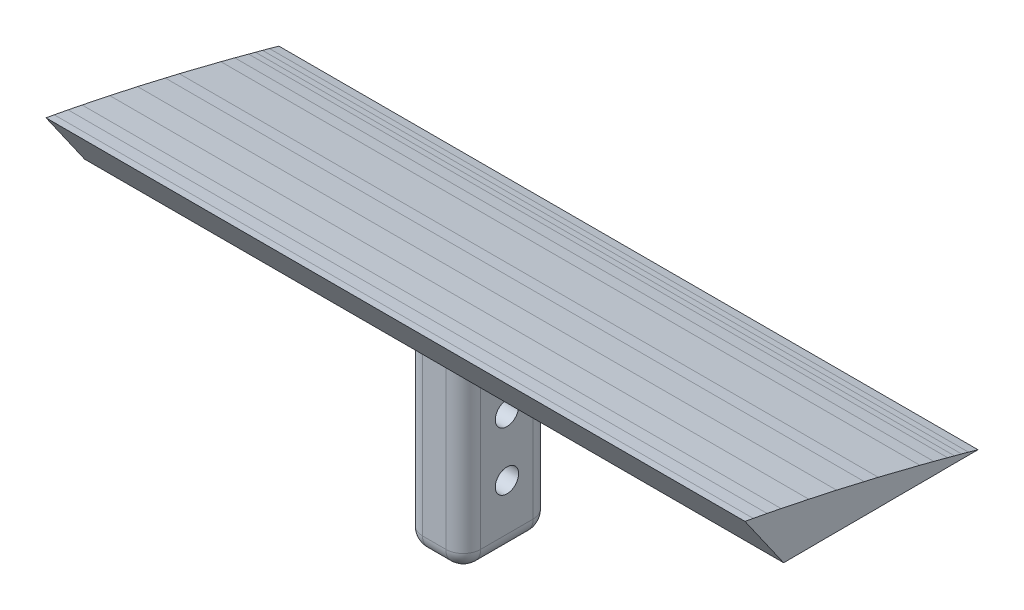
SolidWorks part; units mm, degrees
material "LW PLA"
ref_plane "Front Plane" through (0, 0, 0) normal (0, 0, 1) x (1, 0, 0)
ref_plane "Top Plane" through (0, 0, 0) normal (0, 1, 0) x (1, 0, 0)
ref_plane "Right Plane" through (0, 0, 0) normal (1, 0, 0) x (0, 0, -1)
sketch "Sketch4" plane through (0, 0, 0) normal (1, 0, 0) x (0, 0, -1)
  line L123 (0, 0) -> (68.4812, 0) construction
  line B0 (45.1998, 6.9232) -> (45.1998, 2.1781) construction
  line B1 (65.1998, 2.25) -> (64.3732, 2.4866)
  line B2 (64.3732, 2.4866) -> (63.783, 2.6455)
  line B3 (63.783, 2.6455) -> (63.1827, 2.8045)
  line B4 (63.1827, 2.8045) -> (62.5924, 2.9634)
  line B5 (62.5924, 2.9634) -> (61.4018, 3.2813)
  line B6 (61.4018, 3.2813) -> (60.2113, 3.5892)
  line B7 (60.2113, 3.5892) -> (59.0208, 3.8871)
  line B8 (59.0208, 3.8871) -> (57.8302, 4.185)
  line B9 (57.8302, 4.185) -> (56.6397, 4.4829)
  line B10 (56.6397, 4.4829) -> (55.4392, 4.7608)
  line B11 (55.4392, 4.7608) -> (54.2487, 5.0387)
  line B12 (54.2487, 5.0387) -> (53.0582, 5.3166)
  line B13 (53.0582, 5.3166) -> (51.8678, 5.5745)
  line B14 (51.8678, 5.5745) -> (50.6773, 5.8324)
  line B15 (50.6773, 5.8324) -> (49.4869, 6.0803)
  line B16 (49.4869, 6.0803) -> (48.2964, 6.3282)
  line B17 (48.2964, 6.3282) -> (47.096, 6.5661)
  line B18 (47.096, 6.5661) -> (45.9056, 6.794)
  line B19 (45.9056, 6.794) -> (45.1998, 6.9232)
  line B20 (45.1998, 2.1781) -> (45.7538, 2.1837) construction
  line B21 (45.7538, 2.1837) -> (46.9537, 2.1858) construction
  line B22 (46.9537, 2.1858) -> (48.1537, 2.1879) construction
  line B23 (48.1537, 2.1879) -> (48.515, 2.1886) construction
  line B24 (49.3537, 2.19) -> (50.5537, 2.1922)
  line B25 (50.5537, 2.1922) -> (51.7537, 2.2043)
  line B26 (51.7537, 2.2043) -> (52.9537, 2.2064)
  line B27 (52.9537, 2.2064) -> (54.1537, 2.2085)
  line B28 (54.1537, 2.2085) -> (55.3637, 2.2107)
  line B29 (55.3637, 2.2107) -> (56.5637, 2.2128)
  line B30 (56.5637, 2.2128) -> (57.7637, 2.2249)
  line B31 (57.7637, 2.2249) -> (58.9637, 2.227)
  line B32 (58.9637, 2.227) -> (60.1637, 2.2291)
  line B33 (60.1637, 2.2291) -> (61.3637, 2.2313)
  line B34 (61.3637, 2.2313) -> (62.5637, 2.2434)
  line B35 (62.5637, 2.2434) -> (63.1637, 2.2444)
  line B36 (63.1637, 2.2444) -> (63.7637, 2.2455)
  line B37 (63.7637, 2.2455) -> (64.3637, 2.2466)
  line B38 (64.3637, 2.2466) -> (64.9637, 2.2476)
  line B39 (5, 4.2717) -> (65.0821, 2.2837) construction
  line B40 (64.9637, 2.2476) -> (65.1998, 2.25)
  line B41 (45.1998, 6.9232) -> (48.515, 2.1886)
  line B42 (48.515, 2.1886) -> (49.3537, 2.19)
  dimension "D1" = 1.895
sketch_block_instance "Block2-1"
sketch_block "Block2" parameters "D1"=20, "D2"=3.6418
extrude "Boss-Extrude1" add sketch "Sketch4" along normal blind 60
ref_plane "Plane1" through (0, 2.1886, 0) normal (0, 1, 0) x (1, 0, 0)
sketch "Sketch5" plane through (0, 2.1886, 0) normal (0, 1, 0) x (1, 0, 0)
  line L0 (60, 48.515) -> (0, 48.515) construction
  line L1 (27.5, 48.515) -> (32.5, 48.515)
  line L2 (27.5, 48.515) -> (27.5, 56.015)
  line L3 (27.5, 56.015) -> (32.5, 56.015)
  line L4 (32.5, 48.515) -> (32.5, 56.015)
  point P6 (30, 48.515)
  point P7 (30, 48.515)
  dimension "D1" = 5
  dimension "D2" = 7.5
extrude "Boss-Extrude2" add sketch "Sketch5" along normal up to next and the other way blind 15
fillet "Fillet1" radius 1.5 8 edges at (27.5, -5.2998, -56.015) (30, -12.8114, -56.015) (27.5, -12.8114, -52.265) (27.5, -5.3114, -48.515) (30, -12.8114, -48.515) (32.5, -5.2998, -56.015) (32.5, -5.3114, -48.515) (32.5, -12.8114, -52.265)
sketch "Sketch6" plane through (27.5, 0, 0) normal (-1, 0, 0) x (0, 0, 1)
  line L0 (-54.515, -11.3114) -> (-50.015, -11.3114) construction
  circle A0 centre (-52.265, -7.3114) radius 1
  circle A1 centre (-52.265, -2.3114) radius 1
  point P7 (-52.265, -11.3114)
  dimension "D3" = 2
  dimension "D1" = 5
  dimension "D2" = 4
extrude "Cut-Extrude1" cut sketch "Sketch6" against normal up to next
